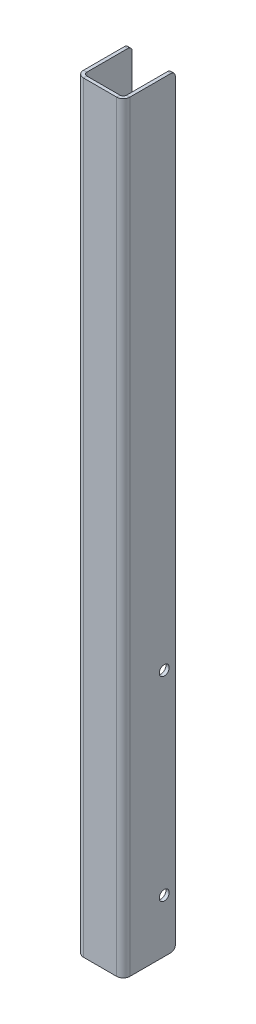
SolidWorks part; units mm, degrees
note: '?' marks a value the reader was unsure of. The reader was unsure of these and kept them because the rebuilt part matched: flange length of "Edge-Flange1".
material "Low Carbon Steel"
ref_plane "Front Plane" through (0, 0, 0) normal (0, 0, 1) x (1, 0, 0)
ref_plane "Top Plane" through (0, 0, 0) normal (0, 1, 0) x (1, 0, 0)
ref_plane "Right Plane" through (0, 0, 0) normal (1, 0, 0) x (0, 0, -1)
sketch "Sketch1" plane through (0, 0, 0) normal (0, 0, 1) x (1, 0, 0)
  line L1 (28.575, 0) -> (-28.575, 0)
  line L2 (28.575, 0) -> (28.575, 1092.2)
  line L3 (28.575, 1092.2) -> (-28.575, 1092.2)
  line L4 (-28.575, 0) -> (-28.575, 1092.2)
  dimension "D1" = 1092.2
  dimension "D2" = 57.15
base flange "Base-Flange1" sketch "Sketch1" thickness 4.7625 reverse thickness direction no parameters "D1"=4.7625
edge flange "Edge-Flange1" sketch "Sketch4" flange profiles "Sketch4", "Sketch13" flange angle 90 flange length 69.85 flange position material outside bend radius 4.7625 thickness 4.7625 relief rectangular parameters "D6"=10, "D8"=1
sketch "Sketch4" plane through (-28.575, 0, -4.7625) normal (1, 0, 0) x (0, -1, 0)
  line L2 (-1092.2, 0) -> (-1092.2, 69.85)
  line L4 (0, 69.85) -> (0, 0)
  line L5 (0, 0) -> (-1092.2, 0) construction
  line L6 (0, 0) -> (-1092.2, 0)
  line L10 (-1092.2, 69.85) -> (0, 69.85)
  dimension "D3" = 69.85
sketch "Sketch13" plane through (28.575, 0, -4.7625) normal (-1, 0, 0) x (0, 1, 0)
  line L0 (1092.2, 0) -> (0, 0) construction
  line L1 (1092.2, 0) -> (0, 0)
  line L2 (1092.2, 0) -> (1092.2, 69.85)
  line L3 (1092.2, 69.85) -> (0, 69.85)
  line L4 (0, 69.85) -> (0, 0)
  line L8 (1092.2, 69.85) -> (0, 69.85) construction
bend "EdgeBend1" bend radius 4.7625 bend angle 90 parameters "D5"=1
bend "EdgeBend4" bend radius 4.7625 bend angle 90 parameters "D5"=3
sketch "Sketch11" plane through (0, 0, 0) normal (0, 1, 0) x (1, 0, 0)
  line L0 (0, 4.7625) -> (0, 31.7625) construction
  line L2 (23.8125, 4.7625) -> (-23.8125, 4.7625) construction
  circle A0 centre (0, 31.7625) radius 18 construction
  dimension "D1" = 36
  dimension "D2" = 27
ref_axis "Axis1" through (0, 0, -31.7625) along (0, 1, 0)?
hole_wizard "1/2 Clearance Hole1" positions "Sketch14" profile "Sketch15" hole size "1/2" standard "Peddi Ansi Inch" end condition through all
sketch "Sketch14" plane through (33.3375, 0, 0) normal (1, 0, 0) x (0, 0, -1)
  line L0 (74.6125, 0) -> (9.525, 0) construction
  line L1 (74.6125, 1092.2) -> (74.6125, 0) construction
  point P0 (58.7375, 76.2)
  point P2 (58.7375, 355.6)
  dimension "D1" = 76.2
  dimension "D2" = 15.875
  dimension "D3" = 279.4
sketch "Sketch15" plane through (33.3375, 76.2, -58.7375) normal (0, 1, 0) x (0, 0, -1)
  line L0 (0, 0) -> (0, 66.675)
  line L1 (0, 66.675) -> (7.1437, 66.675)
  line L2 (7.1437, 66.675) -> (7.1437, 0)
  line L5 (7.1437, 0) -> (0, 0)
  line L11 (0, -6.35) -> (0, 107.95) construction
  dimension "Thru Hole Dia." = 14.2875
  dimension "Thru Hole Depth" = 66.675
fillet "Fillet1" radius 6.35 4 edges at (-30.9563, 1092.2, -74.6125) (30.9563, 1092.2, -74.6125) (-30.9563, 0, -74.6125) (30.9563, 0, -74.6125)
other "Freeze***"
sketch "Bend-Lines1" [suppressed] plane through (0, 0, 0) normal (0, 1, 0) x (1, 0, 0)
sketch "Bounding-Box1" [suppressed] plane through (0, 0, 0) normal (0, 1, 0) x (1, 0, 0)
sheet metal parameters "Sheet-Metal1" thickness 4.7625 parameters "D1"=6.35
flat pattern "Flat-Pattern1" [suppressed]
sketch "Bend-Lines2" plane through (0, 0, 0) normal (0, 0, 1) x (1, 0, 0)
  line L0 (-126.438, 1092.2) -> (-126.438, 0) construction
  line L1 (-126.438, 1092.2) -> (-126.438, 0) construction
sketch3d "Bounding-Box2" [suppressed]
  line L0 (0, 1092.2, 0) -> (0, 0, 0) construction
  line L1 (-252.8761, 1092.2, 0) -> (-252.8761, 0, 0) construction
  line L2 (0, 1092.2, 0) -> (-252.8761, 1092.2, 0) construction
  line L3 (0, 0, 0) -> (-252.8761, 0, 0) construction
sheet metal parameters "Sheet-Metal2" thickness 4.7625 parameters "D1"=6.35
flat pattern "Flat-Pattern1" [suppressed]
sketch "Bend-Lines2" plane through (0, 0, 0) normal (0, 0, 1) x (1, 0, 0)
  line L0 (-126.438, 1092.2) -> (-126.438, 0) construction
  line L1 (-126.438, 1092.2) -> (-126.438, 0) construction
sketch3d "Bounding-Box2" [suppressed]
  line L0 (0, 1092.2, 0) -> (0, 0, 0) construction
  line L1 (-252.8761, 1092.2, 0) -> (-252.8761, 0, 0) construction
  line L2 (0, 1092.2, 0) -> (-252.8761, 1092.2, 0) construction
  line L3 (0, 0, 0) -> (-252.8761, 0, 0) construction
bend of the flat pattern "Flatten-<EdgeBend1>1"
bend of the flat pattern "Flatten-<EdgeBend4>1"
sheet metal parameters "Sheet-Metal5" thickness 4.7625 parameters "D1"=6.35
flat pattern "Flat-Pattern1"
sketch "Bend-Lines2" plane through (0, 0, 0) normal (0, 0, 1) x (1, 0, 0)
  line L2 (29.0491, 0) -> (29.0491, 1092.2) construction
  line L3 (-29.0491, 1092.2) -> (-29.0491, 0) construction
  line L4 (29.0491, 0) -> (29.0491, 1092.2) construction
  line L5 (-29.0491, 1092.2) -> (-29.0491, 0) construction
  point P0 (-126.438, 1092.2)
  point P1 (-126.438, 0)
sketch3d "Bounding-Box2" [suppressed]
  line L0 (99.3732, 0, 0) -> (99.3733, 1092.2, 0) construction
  line L1 (-99.3733, 0, 0) -> (-99.3732, 1092.2, 0) construction
  line L2 (99.3732, 0, 0) -> (-99.3733, 0, 0) construction
  line L3 (99.3733, 1092.2, 0) -> (-99.3732, 1092.2, 0) construction
bend of the flat pattern "Flatten-<EdgeBend1>1"
bend of the flat pattern "Flatten-<EdgeBend4>1"
